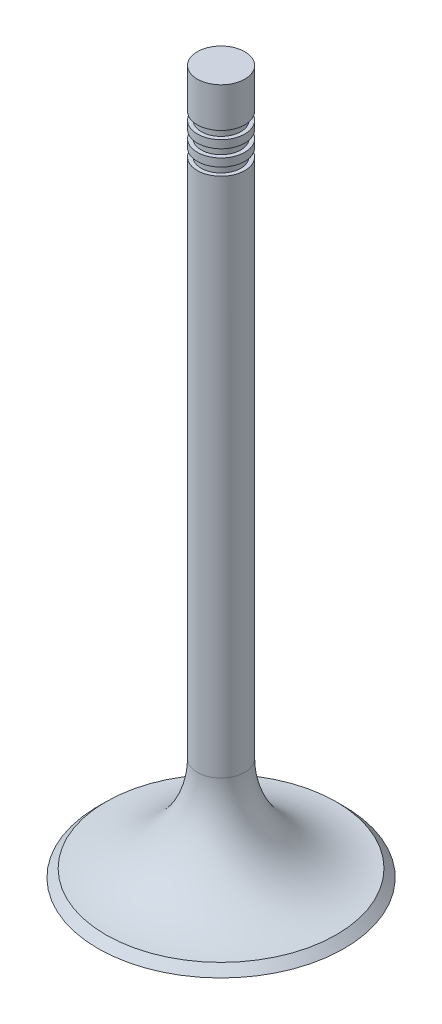
SolidWorks part; units mm, degrees
ref_plane "Front Plane" through (0, 0, 0) normal (0, 0, 1) x (1, 0, 0)
ref_plane "Top Plane" through (0, 0, 0) normal (0, 1, 0) x (1, 0, 0)
ref_plane "Right Plane" through (0, 0, 0) normal (1, 0, 0) x (0, 0, -1)
sketch "Sketch1" plane through (0, 0, 0) normal (0, 1, 0) x (1, 0, 0)
  circle A0 centre (0, 0) radius 15.55
  dimension "D1" = 31.1
extrude "Boss-Extrude1" add sketch "Sketch1" along normal blind 1
chamfer "Chamfer2" distance 1 angle 45 1 edges at (0, 1, 15.55)
sketch "Sketch4" plane through (0, 1, 0) normal (0, 1, 0) x (1, 0, 0)
  circle A0 centre (0, 0) radius 3
  dimension "D1" = 6
extrude "Boss-Extrude2" add sketch "Sketch4" along normal blind 87.8
fillet "Fillet1" radius 12 1 edges at (0, 1, 3)
sketch "Sketch5" plane through (0, 0, 0) normal (0, 0, 1) x (1, 0, 0)
  line L0 (0, 88.8) -> (0, 0) construction
  line L1 (3, 88.8) -> (-3, 88.8) construction
  line L2 (-3, 88.8) -> (-3, 83.8) construction
  line L3 (-3, 88.8) -> (-3, 12.9916) construction
  line L4 (-3, 83.8) -> (-3, 82.8)
  line L5 (-3, 82.8) -> (-3, 81.8)
  line L6 (-3, 81.8) -> (-3, 80.8)
  line L7 (-3, 80.8) -> (-3, 79.8)
  line L8 (-3, 79.8) -> (-3, 78.8)
  line L9 (-3, 78.8) -> (-3, 77.8)
  line L11 (-3, 83.8) -> (-2.5, 83.8)
  line L12 (-3, 83.8) -> (-3, 82.8)
  line L13 (-3, 82.8) -> (-2.5, 82.8)
  line L14 (-2.5, 83.8) -> (-2.5, 82.8)
  line L15 (-3, 81.8) -> (-2.5, 81.8)
  line L16 (-3, 81.8) -> (-3, 80.8)
  line L17 (-3, 80.8) -> (-2.5, 80.8)
  line L18 (-2.5, 81.8) -> (-2.5, 80.8)
  line L19 (-3, 79.8) -> (-2.5, 79.8)
  line L20 (-3, 79.8) -> (-3, 78.8)
  line L21 (-3, 78.8) -> (-2.5, 78.8)
  line L22 (-2.5, 79.8) -> (-2.5, 78.8)
  dimension "D1" = 5
  dimension "D2" = 1
  dimension "D3" = 1
  dimension "D4" = 1
  dimension "D5" = 1
  dimension "D6" = 1
  dimension "D7" = 1
  dimension "D8" = 0.5
revolve "Cut-Revolve1" cut sketch "Sketch5" angle 360 about L0 region at (-2.75, 83.3, 0) region at (-2.75, 79.3, 0) region at (-2.75, 81.3, 0)
